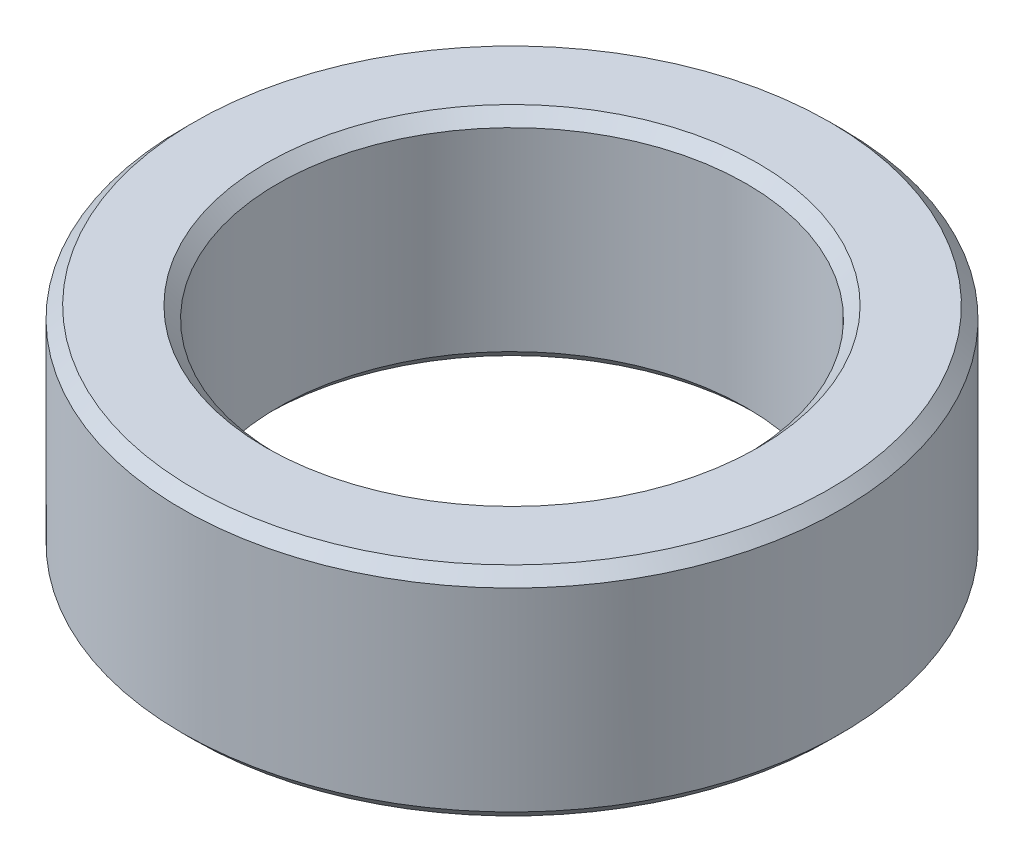
SolidWorks part; units mm, degrees
ref_plane "Front Plane" through (0, 0, 0) normal (0, 0, 1) x (1, 0, 0)
ref_plane "Top Plane" through (0, 0, 0) normal (0, 1, 0) x (1, 0, 0)
ref_plane "Right Plane" through (0, 0, 0) normal (1, 0, 0) x (0, 0, -1)
sketch "Sketch1" plane through (0, 0, 0) normal (0, 1, 0) x (1, 0, 0)
  circle A0 centre (0, 0) radius 50
  dimension "SLEEVE_OD" = 100
extrude "Boss-Extrude1" add sketch "Sketch1" along normal blind 32.9915
sketch "Sketch2" plane through (0, 0, 0) normal (0, 1, 0) x (1, 0, 0)
  circle A0 centre (0, 0) radius 35.5649
  dimension "BORE_D" = 71.1298
extrude "Cut-Extrude1" cut sketch "Sketch2" along normal through all
chamfer "Chamfer1" distance 1.7844 angle 45 4 edges at (0, 32.9915, 35.5649) (0, 0, 35.5649) (0, 0, 50) (0, 32.9915, 50)
